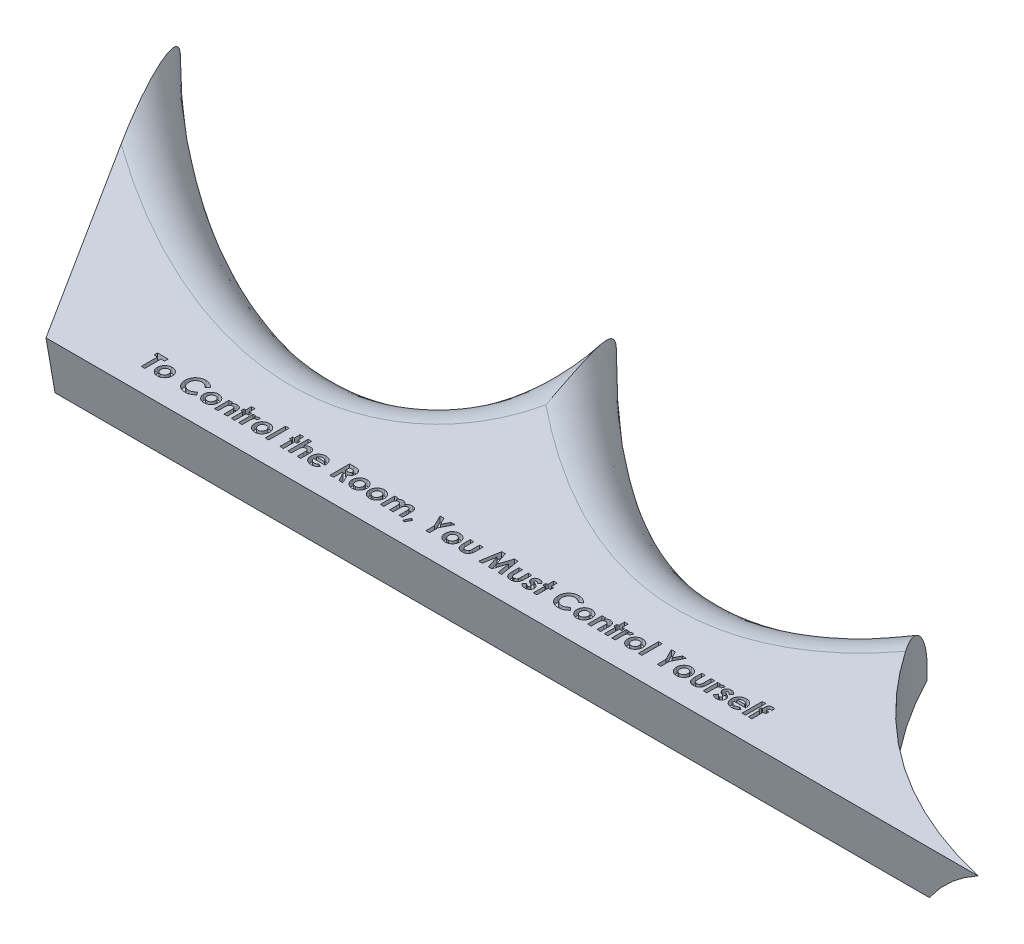
SolidWorks part; units mm, degrees
ref_plane "Front Plane" through (0, 0, 0) normal (0, 0, 1) x (1, 0, 0)
ref_plane "Top Plane" through (0, 0, 0) normal (0, 1, 0) x (1, 0, 0)
ref_plane "Right Plane" through (0, 0, 0) normal (1, 0, 0) x (0, 0, -1)
sketch "Sketch1" plane through (0, 0, 0) normal (0, 1, 0) x (1, 0, 0)
  line L0 (57.8783, 2.8969) -> (-107.1217, 2.8969)
  line L1 (57.8783, 2.8969) -> (26.9924, 10.1667) construction
  line L2 (26.9924, 10.1667) -> (11.3749, 40.3963) construction
  line L3 (11.3749, 40.3963) -> (-9.3133, 5.6978) construction
  line L4 (-9.3133, 5.6978) -> (-64.7345, 61.4824) construction
  line L5 (-64.7345, 61.4824) -> (-48.2707, 6.5318) construction
  line L6 (-48.2707, 6.5318) -> (-104.9319, 24.4923) construction
  line L7 (-104.9319, 24.4923) -> (-148.3365, 67.8969) construction
  line L8 (-148.3365, 67.8969) -> (-107.1217, 2.8969)
  spline S0 degree 2 poles (57.8783, 2.8969) (26.9924, 10.1667) (11.3749, 40.3963) knots 0 0 0 1 1 1
  spline S1 degree 2 poles (11.3749, 40.3963) (-9.3133, 5.6978) (-64.7345, 61.4824) knots 0 0 0 1 1 1
  spline S2 degree 3 poles (-64.7345, 61.4824) (-48.2707, 6.5318) (-104.9319, 24.4923) (-148.3365, 67.8969) knots 0 0 0 0 1 1 1 1
  point P9 (-94.2411, 49.5088)
  point P10 (-23.4468, -7.3662)
  point P11 (-69.8661, 49.2949)
  point P12 (-57.0372, 9.3114)
  point P13 (-68.1556, 51.2193)
  point P14 (-148.3365, 67.8969)
  point P15 (-78.4188, 11.2357)
  point P16 (-104.9319, 24.4923)
  point P17 (-64.7345, 61.4824)
  point P18 (-48.2707, 6.5318)
  dimension "D1" = 65
  dimension "D2" = 165
extrude "Boss-Extrude1" add sketch "Sketch1" along normal blind 12 contours L0 L8 S2 S1 S0
fillet "Fillet6" radius 10 2 edges
ref_plane "Plane2" through (57.8783, 0, -2.8969) normal (-1, 0, 0) x (0, 0, 1)
sketch "Sketch6" plane through (57.8783, 0, -2.8969) normal (-1, 0, 0) x (0, 0, 1)
  line L0 (7.86, 33.5952) -> (-4.3676, 0)
  line L1 (-4.3676, 0) -> (9.8257, -4.2001)
  line L2 (7.86, 33.5952) -> (9.8257, -4.2001)
  line L3 (-37.4994, 0) -> (0, 0) construction
  point P3 (-14.345, -4.644)
  point P4 (0, 0)
  point P5 (0, 0)
  point P7 (0, 0)
  point P10 (-3.6937, 0)
  point P11 (13.8335, -4.2381)
  point P12 (-4.3676, 0)
  dimension "D1" = 70
extrude "Cut-Extrude3" cut sketch "Sketch6" along normal through all contours L2 L1 L0
sketch "Sketch7" plane through (0, 12, 0) normal (0, 1, 0) x (1, 0, 0)
  text T0 "<b>To Control the Room, You Must Control Yourself</b>"
extrude "Cut-Extrude5" cut sketch "Sketch7" against normal blind 1
